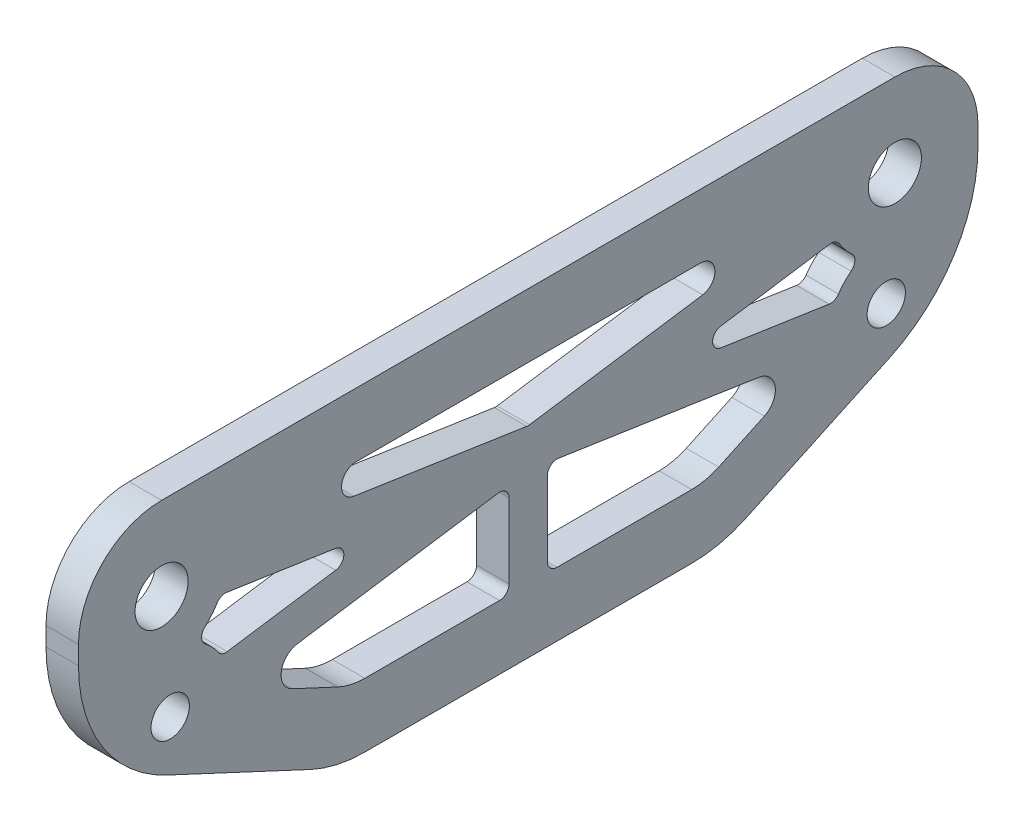
SolidWorks part; units mm, degrees
ref_plane "Front Plane" through (0, 0, 0) normal (0, 0, 1) x (1, 0, 0)
ref_plane "Top Plane" through (0, 0, 0) normal (0, 1, 0) x (1, 0, 0)
ref_plane "Right Plane" through (0, 0, 0) normal (1, 0, 0) x (0, 0, -1)
sketch "Sketch1" plane through (0, 0, 0) normal (1, 0, 0) x (0, 0, -1)
  line L0 (15, 12.5) -> (28.675, 12.5)
  line L1 (-15, -12.5) -> (15, -12.5)
  line L3 (-15, 12.5) -> (15, 12.5)
  line L5 (-15, -12.5) -> (15, 12.5) construction
  line L6 (-15, 12.5) -> (15, -12.5) construction
  line L8 (0, 12.5) -> (0, -12.5) construction
  line L10 (-15, 12.5) -> (-28.675, 12.5)
  line L11 (23.175, 98.3219) -> (23.175, -129.0781) construction
  line L13 (35.175, 6) -> (35.175, 4.5526)
  line L14 (28.2464, -6.3231) -> (15, -12.5)
  line L16 (-35.175, 6) -> (-35.175, 4.5526)
  line L17 (-28.2464, -6.3231) -> (-15, -12.5)
  arc A0 (28.675, 12.5) -> (35.175, 6) centre (28.675, 6) cw
  circle A1 centre (28.675, 6) radius 5.5 construction
  circle A2 centre (-28.675, 6) radius 5.5 construction
  arc A3 (-28.675, 12.5) -> (-35.175, 6) centre (-28.675, 6) ccw
  arc A4 (35.175, 4.5526) -> (28.2464, -6.3231) centre (23.175, 4.5526) cw
  circle A5 centre (28.675, 6) radius 2.075
  arc A6 (-35.175, 4.5526) -> (-28.2464, -6.3231) centre (-23.175, 4.5526) ccw
  circle A9 centre (-28.675, 6) radius 2.075
  circle A11 centre (28, -2.5) radius 1.5
  circle A12 centre (-28, -2.5) radius 1.5
  point P0 (0, 0)
  point P28 (0, 0)
  dimension "D1" = 11
  dimension "D2" = 1
  dimension "D3" = 4.15
  dimension "D4" = 3
  dimension "D6" = 25
  dimension "D8" = 12
  dimension "D5" = 25
  dimension "D7" = 30
  dimension "D9" = 28
  dimension "D10" = 2.5
extrude "Boss-Extrude1" add sketch "Sketch1" along normal blind 2.54
fillet "Fillet1" radius 10 2 edges at (1.27, -12.5, -15) (1.27, -12.5, 15)
sketch "Sketch2" plane through (0, 0, 0) normal (1, 0, 0) x (0, 0, -1)
  line L0 (-28.675, 6) -> (28, -2.5) construction
  line L10 (-28.675, -2.6012) -> (28.675, 6)
  line L11 (-28.675, 6) -> (28, -2.5)
  line L12 (-28.8975, 4.5166) -> (27.7775, -3.9834)
  line L13 (-28.4525, 7.4834) -> (28.2225, -1.0166)
  line L14 (-28.8975, 4.5166) -> (-28.4525, 7.4834)
  line L15 (27.7775, -3.9834) -> (28.2225, -1.0166)
  line L16 (-12.7831, -7.5) -> (12.7831, -7.5)
  line L17 (14.8961, -7.0315) -> (26.1333, -1.7916)
  line L18 (30.175, 4.5526) -> (30.175, 6)
  line L19 (28.675, 7.5) -> (-28.675, 7.5)
  line L20 (-30.175, 6) -> (-30.175, 4.5526)
  line L21 (-26.1333, -1.7916) -> (-14.8961, -7.0315)
  line L22 (-12.7831, -7.5) -> (12.7831, -7.5)
  line L23 (14.8961, -7.0315) -> (26.1333, -1.7916)
  line L24 (30.175, 4.5526) -> (30.175, 6)
  line L25 (28.675, 7.5) -> (-28.675, 7.5)
  line L26 (-30.175, 6) -> (-30.175, 4.5526)
  line L27 (-26.1333, -1.7916) -> (-14.8961, -7.0315)
  line L28 (-28.4525, -4.0846) -> (28.8975, 4.5166)
  line L29 (-28.8975, -1.1178) -> (28.4525, 7.4834)
  line L30 (-28.4525, -4.0846) -> (-28.8975, -1.1178)
  line L31 (28.8975, 4.5166) -> (28.4525, 7.4834)
  line L32 (0, -7.5) -> (0, 7.5) construction
  line L33 (0, 1.6994) -> (0, -7.5)
  line L34 (-1.5, 1.6994) -> (-1.5, -7.5)
  line L35 (1.5, 1.6994) -> (1.5, -7.5)
  line L36 (-1.5, 1.6994) -> (1.5, 1.6994)
  line L37 (-1.5, -7.5) -> (1.5, -7.5)
  arc A0 (-18.0527, -2.5249) -> (-18.4641, -5.3678) centre (-17.8302, -4.0083) ccw
  arc A1 (18.0527, -2.5249) -> (18.4641, -5.3678) centre (17.8302, -4.0083) cw
  circle A2 centre (-28, -2.5) radius 4.5
  circle A3 centre (-28, -2.5) radius 4.5
  circle A5 centre (28, -2.5) radius 4.5
  circle A6 centre (28, -2.5) radius 4.5
  circle A11 centre (-28.675, 6) radius 5.075
  arc A12 (12.7831, -7.5) -> (14.8961, -7.0315) centre (12.7831, -2.5) ccw
  arc A13 (26.1333, -1.7916) -> (30.175, 4.5526) centre (23.175, 4.5526) ccw
  arc A14 (30.175, 6) -> (28.675, 7.5) centre (28.675, 6) ccw
  arc A15 (-28.675, 7.5) -> (-30.175, 6) centre (-28.675, 6) ccw
  arc A16 (-30.175, 4.5526) -> (-26.1333, -1.7916) centre (-23.175, 4.5526) ccw
  arc A17 (-14.8961, -7.0315) -> (-12.7831, -7.5) centre (-12.7831, -2.5) ccw
  arc A18 (12.7831, -7.5) -> (14.8961, -7.0315) centre (12.7831, -2.5) ccw
  arc A19 (26.1333, -1.7916) -> (30.175, 4.5526) centre (23.175, 4.5526) ccw
  arc A20 (30.175, 6) -> (28.675, 7.5) centre (28.675, 6) ccw
  arc A21 (-28.675, 7.5) -> (-30.175, 6) centre (-28.675, 6) ccw
  arc A22 (-30.175, 4.5526) -> (-26.1333, -1.7916) centre (-23.175, 4.5526) ccw
  arc A23 (-14.8961, -7.0315) -> (-12.7831, -7.5) centre (-12.7831, -2.5) ccw
  circle A24 centre (-28.675, 6) radius 5.075
  circle A26 centre (28.675, 6) radius 5.075
  circle A27 centre (28.675, 6) radius 5.075
  arc A32 (13.477, 7.5) -> (13.6439, 5.2624) centre (13.477, 6.375) cw
  arc A33 (-13.477, 7.5) -> (-13.6439, 5.2624) centre (-13.477, 6.375) ccw
  dimension "D11" = 3
  dimension "D12" = 1.125
  dimension "D2" = 1.5
  dimension "D1" = 5
  dimension "D3" = 3
  dimension "D4" = 3
  dimension "D6" = 1.5
  dimension "D7" = 1.5
  dimension "D8" = 1.5
  dimension "D9" = 1.5
  dimension "D13" = 1.5
  dimension "D14" = 1.5
  dimension "D15" = 3
extrude "Cut-Extrude2" cut sketch "Sketch2" along normal through all contours A24 A3 L29 L12 | A27 L28 L13 A6 | L25 A33 L13 L29 A32 | A1 L12 L35 L22 | L28 A0 L22 L34 region at (0, 1.7005, 19.9688) region at (0, -4.2389, 9.1911) region at (0, 5.8357, 0) region at (0, -4.2389, -9.1911) region at (0, 1.7005, -19.9688)
fillet "Fillet2" radius 0.75 13 edges at (1.27, -7.5, -1.5) (1.27, 3.7975, -24.1028) (1.27, 1.6994, -10.1133) (1.27, 3.7975, 24.1028) (1.27, 3.2162, 0) (1.27, -0.0424, -1.5) (1.27, -7.5, 1.5) (1.27, -0.0424, 1.5) (1.27, 1.6994, 10.1133) (1.27, -0.3873, -24.0268) (1.27, 1.6002, -26.1457) (1.27, -0.3873, 24.0268) (1.27, 1.6002, 26.1457)
